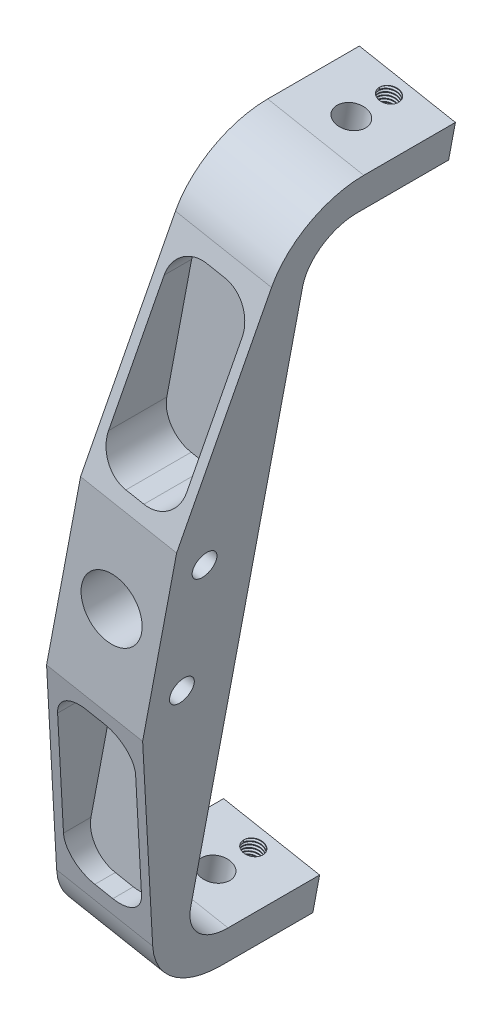
SolidWorks part; units mm, degrees
other "Markup1"
sketch "Sketch6" plane through (39.3536, 123.4271, -45) normal (0.998, 0.0328, -0.0532) x (-0.0595, 0.2351, -0.9701)
other "Markup2"
sketch "Sketch7" plane through (39.3536, 123.4271, -45) normal (0.9999, 0.0057, -0.0131) x (0.0031, -0.9818, -0.1901)
other "Markup4"
sketch "Sketch9" plane through (-39.3536, 123.4271, 27) normal (-0.9915, 0.1233, 0.0413) x (-0.1205, -0.9906, 0.0646)
other "Markup5"
sketch "Sketch12" plane through (-39.3536, 123.4271, 28.5) normal (-0.7749, 0.0474, 0.6304) x (0.632, 0.0395, 0.7739)
material "6061-T6 (SS)"
ref_plane "Front Plane" through (0, 0, 0) normal (0, 0, 1) x (1, 0, 0)
ref_plane "Top Plane" through (0, 0, 0) normal (0, 1, 0) x (1, 0, 0)
ref_plane "Right Plane" through (0, 0, 0) normal (1, 0, 0) x (0, 0, -1)
sketch "Sketch1" plane through (0, 0, 0) normal (0, 0, 1) x (1, 0, 0)
  line L0 (23.3397, 123.7002) -> (23.3397, 145.9252) construction
  line L1 (0, 0) -> (0, -276.86) construction
  line L2 (0, -276.86) -> (-52.2377, -276.86) construction
  line L3 (23.3397, 123.7002) -> (-52.2377, -276.86) construction
  line L8 (-23.3397, -123.7002) -> (-27.4603, -145.5398) construction
  line L9 (-7.6171, -126.6667) -> (39.0622, 120.7336)
  line L14 (-39.0622, -120.7336) -> (7.6171, 126.6667)
  line L17 (23.3397, 123.7002) -> (27.4603, 145.5398) construction
  line L19 (-7.6171, -126.6667) -> (-39.0622, -120.7336)
  line L20 (-23.3397, -123.7002) -> (-25.4, -134.62) construction
  line L21 (7.6171, 126.6667) -> (39.0622, 120.7336)
  line L22 (23.3397, 123.7002) -> (-23.3397, -123.7002) construction
  circle A0 centre (0, 0) radius 276.86 construction
  circle A1 centre (0, 0) radius 10
  circle A2 centre (0, 0) radius 170.5 construction
  point P4 (25.4, 134.62)
  point P6 (0, 0)
  point P10 (0, -170.5)
  point P13 (-10.5081, -129.9032)
  point P17 (0, 0)
  point P18 (41.7595, 124.248)
  point P19 (-41.8145, -123.9803)
  point P20 (10.5081, 129.9032)
  point P25 (-25.4, -134.62)
  point P31 (0, 0)
  point P32 (-23.3397, -123.7002)
  dimension "D4" = 341
  dimension "D9" = 20
  dimension "D2" = 553.72
  dimension "D3" = 22.225
  dimension "D5" = 50.8
  dimension "D6" = 32
  dimension "D7" = 52.2377
  dimension "D8" = 251.7655
  dimension "D11" = 11.1125
  dimension "D12" = 269.24
extrude "Boss-Extrude1" add sketch "Sketch1" along normal blind 28.5
sketch "Sketch2" plane through (0, 0, 0) normal (0, 0, -1) x (-1, 0, 0)
  line L0 (-36.8373, 108.9417) -> (-5.3922, 114.8748)
  line L1 (5.3922, -114.8748) -> (36.8373, -108.9417)
  line L2 (-5.3922, 114.8748) -> (-7.6171, 126.6667)
  line L3 (5.3922, -114.8748) -> (7.6171, -126.6667)
  line L4 (-7.6171, 126.6667) -> (-39.0622, 120.7336)
  line L5 (-39.0622, 120.7336) -> (7.6171, -126.6667)
  line L6 (-7.6171, 126.6667) -> (-39.0622, 120.7336)
  line L7 (39.0622, -120.7336) -> (-7.6171, 126.6667)
  line L9 (-39.0622, 120.7336) -> (-36.8373, 108.9417)
  line L11 (39.0622, -120.7336) -> (36.8373, -108.9417)
  line L14 (7.6171, -126.6667) -> (39.0622, -120.7336)
  line L15 (7.6171, -126.6667) -> (39.0622, -120.7336)
  line M8 (-39.0622, 120.7336) -> (7.6171, -126.6667)
  line M10 (39.0622, -120.7336) -> (-7.6171, 126.6667)
  dimension "D2" = 12
  dimension "D1" = 0
extrude "Boss-Extrude2" add sketch "Sketch2" along normal blind 45 contours L0 M8 M10 | L1 M8 M10 region at (22.2272, 117.8042, 0) region at (-22.2272, -117.8042, 0)
sketch "Sketch4" plane through (-1.6562, 128.4164, 0) normal (0.1854, 0.9827, 0) x (0.9827, -0.1854, 0)
  line L0 (25.4368, -28.5) -> (25.4368, 45) construction
  line L3 (9.4368, 45) -> (41.4368, 45) construction
  line L12 (9.4368, 26.6476) -> (41.4368, 26.6476) construction
  line L13 (9.4368, -28.5) -> (9.4368, 45) construction
  line L14 (41.4368, -28.5) -> (41.4368, 45) construction
  circle A0 centre (25.4368, 26.6476) radius 4.7625
  circle A1 centre (25.4368, 39) radius 3.175
  point P6 (25.4368, 26.6476)
  dimension "D2" = 9.525
  dimension "D3" = 6.35
  dimension "D1" = 18.3524
  dimension "D4" = 6
extrude "Cut-Extrude1" cut sketch "Sketch4" against normal through all contours L0 A0 | L0 A0 | A0 L0 | L0 A0 | A1 region at (23.3397, 123.7002, -26.6476)
fillet "Fillet3" radius 15 2 edges at (21.1148, 111.9082, 0) (-21.1148, -111.9082, 0)
sketch "Sketch10" plane through (-16.0243, 1.3676, 0) normal (0.9827, -0.1854, 0) x (0, 0, -1)
  line L0 (-28.5, 31.6271) -> (-11.3167, 106.5459)
  line L1 (-28.5, 31.6271) -> (-46.9127, 31.4169)
  line L2 (-46.9127, 31.4169) -> (-44.7685, 140.1716)
  line L3 (-44.7685, 140.1716) -> (15, 127.5099)
  line L4 (0, 1.6271) -> (-52.8517, 1.6271) construction
  line L5 (-28.5, 127.5099) -> (45, 127.5099) construction
  line L6 (-28.5, -124.2556) -> (-28.5, 127.5099) construction
  line L7 (-44.7685, -136.9173) -> (15, -124.2556)
  line L8 (-46.9127, -28.1627) -> (-44.7685, -136.9173)
  line L9 (-28.5, -28.3729) -> (-46.9127, -28.1627)
  line L10 (-28.5, -28.3729) -> (-11.3167, -103.2916)
  line L11 (-28.5, 31.6271) -> (0, 31.6271) construction
  line L12 (0, -97.2556) -> (0, 100.5099) construction
  line L13 (-17.5, -18.3729) -> (-17.5, 21.6271) construction
  arc A0 (15, 115.5099) -> (0, 100.5099) centre (15, 100.5099) ccw construction
  arc A1 (15, 115.5099) -> (0, 100.5099) centre (15, 100.5099) ccw construction
  arc A2 (15, 127.5099) -> (-11.3167, 106.5459) centre (15, 100.5099) ccw
  arc A3 (15, -112.2556) -> (0, -97.2556) centre (15, -97.2556) cw construction
  arc A4 (15, -124.2556) -> (-11.3167, -103.2916) centre (15, -97.2556) cw
  circle A5 centre (-17.5, 21.6271) radius 4
  circle A6 centre (-17.5, -18.3729) radius 4
  point P14 (15, 127.5099)
  point P29 (15, -124.2556)
  point P37 (-17.5, 1.6271)
  dimension "D1" = 30
  dimension "D2" = 8
  dimension "D3" = 17.5
  dimension "D4" = 40
extrude "Cut-Extrude2" cut sketch "Sketch10" against normal through all both and the other way through all
sketch "Sketch11" plane through (0, 0, 28.5) normal (0, 0, 1) x (1, 0, 0)
  line L1 (0, 0) -> (75.6649, -14.2764) construction
  line L2 (35.1753, 100.1331) -> (21.2848, 26.5133) construction
  line L3 (35.1753, 100.1331) -> (21.2848, 26.5133) construction
  line L7 (3.5413, 34.9494) -> (9.4373, 33.8369)
  line L12 (-10.1604, 32.4464) -> (3.7302, 106.0662) construction
  line L13 (-10.1604, 32.4464) -> (3.7302, 106.0662) construction
  line L15 (21.118, 41.8095) -> (29.2542, 84.9314)
  line L26 (-4.4312, 46.6301) -> (3.705, 89.752)
  line L27 (2.6111, 100.1348) -> (34.0562, 94.2018) construction
  line L39 (15.3857, 97.7245) -> (21.2816, 96.6121)
  line L40 (-21.2848, -26.5133) -> (-35.1753, -100.1331) construction
  line L41 (-3.7302, -106.0662) -> (10.1604, -32.4464) construction
  line L42 (-21.2816, -96.6121) -> (-15.3857, -97.7245)
  line L43 (-21.118, -41.8095) -> (-29.2542, -84.9314)
  line L44 (4.4312, -46.6301) -> (-3.705, -89.752)
  line L45 (-9.4373, -33.8369) -> (-3.5413, -34.9494)
  arc A0 (9.4373, 33.8369) -> (21.118, 41.8095) centre (11.2913, 43.6636) ccw
  arc A1 (3.5413, 34.9494) -> (-4.4312, 46.6301) centre (5.3954, 44.776) cw
  arc A2 (15.3857, 97.7245) -> (3.705, 89.752) centre (13.5316, 87.8979) ccw
  arc A3 (29.2542, 84.9314) -> (21.2816, 96.6121) centre (19.4275, 86.7855) ccw
  arc A4 (-3.705, -89.752) -> (-15.3857, -97.7245) centre (-13.5316, -87.8979) cw
  arc A5 (-21.2816, -96.6121) -> (-29.2542, -84.9314) centre (-19.4275, -86.7855) cw
  arc A6 (-9.4373, -33.8369) -> (-21.118, -41.8095) centre (-11.2913, -43.6636) ccw
  arc A7 (-3.5413, -34.9494) -> (4.4312, -46.6301) centre (-5.3954, -44.776) cw
  point P12 (-3.4131, 31.3285)
  point P15 (10.5274, 99.16)
  point P16 (29.4323, 95.2747)
  point P17 (15.4917, 27.4432)
  point P18 (27.5728, 26.3797)
  point P19 (-17.6556, 26.3797)
  dimension "D4" = 10
  dimension "D2" = 6
  dimension "D1" = 35
  dimension "D3" = 6
extrude "Cut-Extrude4" cut sketch "Sketch11" against normal offset from surface (22.5 mm away) 6 contours A2 | A4 L42 A5 L43 A6 L45 A7 L44 region at (12.4115, 65.7807, 28.5) up to face at (10, 0, 0)
thread "Thread1" pitch 1.0583 method cut profile "Thread Profile2" start angle 0, offset 0, length 0, pitch 1.0583, diameter 6.35
ref_plane "Plane2" through (20.2197, 124.2888, -39) normal (0, 0, 1) x (-0.9827, 0.1854, 0)
sketch "Thread Profile2" plane through (20.2197, 124.2888, -39) normal (0, 0, 1) x (-0.9827, 0.1854, 0)
  line L0 (0, 0) -> (0, 1.0583) construction
  line L1 (0, 0) -> (0.5728, 0.3307)
  line L2 (0.5728, 0.3307) -> (0.5728, 0.463)
  line L3 (0.5728, 0.463) -> (0, 0.7937)
  line L4 (0.5728, 0.3969) -> (0, 0.3969) construction
  line L11 (0, 0) -> (0, 0.7937)
  point P2 (0, 0)
  dimension "Pitch" = 1.0583
  dimension "Profile_Angle" = 60
  dimension "Profile_Land" = 0.1323
  dimension "Profile_Height" = 0.5728
thread "Thread2" pitch 1.0583 method cut profile "Thread Profile3" start angle 0, offset 0, length 0, pitch 1.0583, diameter 6.35
ref_plane "Plane3" through (-24.2347, -111.3196, -39) normal (0, 0, 1) x (-0.9827, 0.1854, 0)
sketch "Thread Profile3" plane through (-24.2347, -111.3196, -39) normal (0, 0, 1) x (-0.9827, 0.1854, 0)
  line L0 (0, 0) -> (0, 1.0583) construction
  line L1 (0, 0) -> (0.5728, 0.3307)
  line L2 (0.5728, 0.3307) -> (0.5728, 0.463)
  line L3 (0.5728, 0.463) -> (0, 0.7937)
  line L4 (0.5728, 0.3969) -> (0, 0.3969) construction
  line L11 (0, 0) -> (0, 0.7937)
  point P2 (0, 0)
  dimension "Pitch" = 1.0583
  dimension "Profile_Angle" = 60
  dimension "Profile_Land" = 0.1323
  dimension "Profile_Height" = 0.5728
